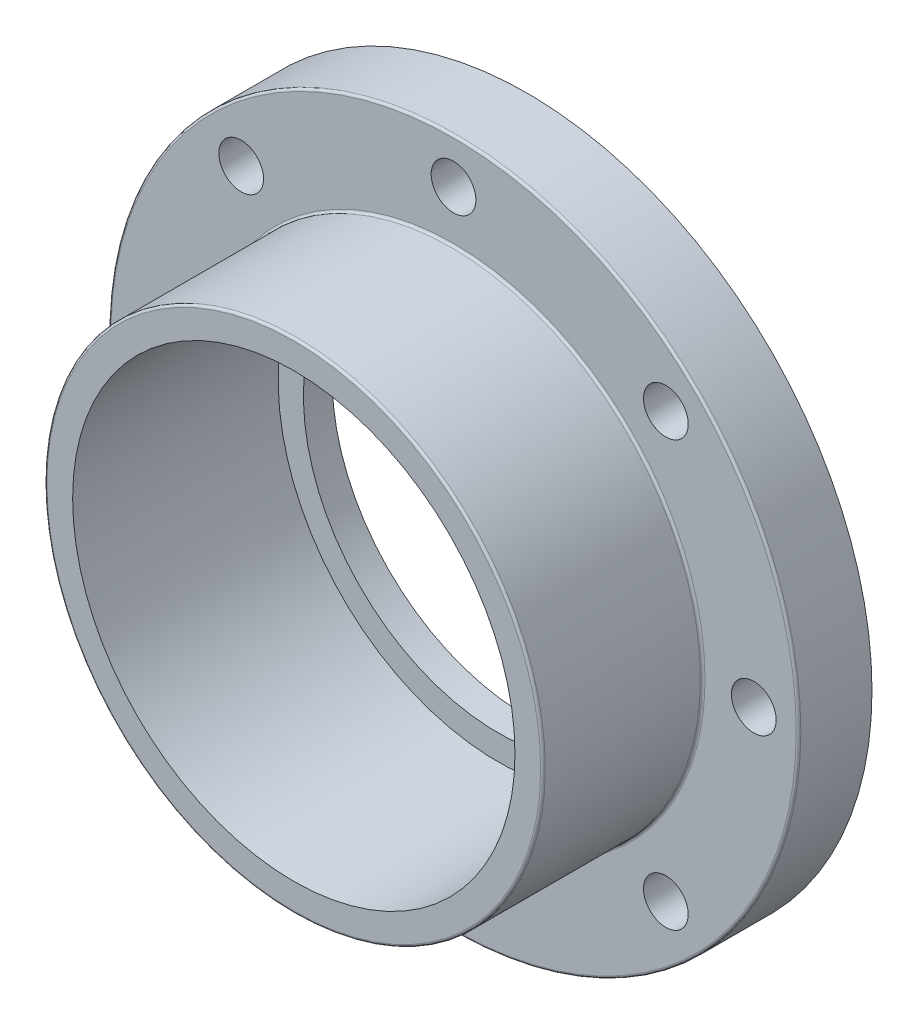
SolidWorks part; units mm, degrees
ref_plane "Front Plane" through (0, 0, 0) normal (0, 0, 1) x (1, 0, 0)
ref_plane "Top Plane" through (0, 0, 0) normal (0, 1, 0) x (1, 0, 0)
ref_plane "Right Plane" through (0, 0, 0) normal (1, 0, 0) x (0, 0, -1)
sketch "Sketch0" plane through (0, 0, 0) normal (1, 0, 0) x (0, 0, -1)
  line L0 (0, 0) -> (-115.8875, 0) construction
  point P3 (-36.5125, 0)
  point P4 (-14.2875, 0)
  dimension "Q" = 36.5125
  dimension "C" = 115.8875
  dimension "N" = 14.2875
sketch "Sketch1" plane through (0, 0, 0) normal (0, 0, 1) x (1, 0, 0)
  circle A0 centre (0, 0) radius 171.45
  circle A1 centre (0, 0) radius 109.9185 construction
  circle A2 centre (0, 0) radius 149.225 construction
  circle A3 centre (0, 149.225) radius 11.1125 construction
  circle A4 centre (0, 0) radius 123.825 construction
  circle A5 centre (0, 0) radius 96.8375 construction
  circle A6 centre (0, 0) radius 109.347 construction
  point P9 (0, 109.9185)
  point P10 (0, 109.347)
  point P11 (0, 96.8375)
  dimension "A" = 342.9
  dimension "B" = 298.45
  dimension "Bolt Hole Size" = 22.225
  dimension "Pipe OD A" = 219.837
  dimension "Hub OD" = 247.65
  dimension "Pipe ID" = 193.675
  dimension "Pipe OD B" = 218.694
extrude "Extrude1" add sketch "Sketch1" along normal up to vertex (36.5125 mm away) up to point (0, 0, 36.5125)
sketch "Sketch2" plane through (0, 0, 36.5125) normal (0, 0, 1) x (1, 0, 0)
  circle A0 centre (0, 0) radius 123.825 construction
  circle A1 centre (0, 0) radius 123.825
extrude "Extrude2" add sketch "Sketch2" along normal up to vertex (79.375 mm away) up to point (0, 0, 115.8875)
sketch "Sketch3" plane through (0, 0, 36.5125) normal (0, 0, 1) x (1, 0, 0)
  circle A0 centre (0, 149.225) radius 11.1125 construction
  circle A1 centre (0, 149.225) radius 11.1125
extrude "Extrude3" cut sketch "Sketch3" against normal through all
ref_axis "Axis1" through (0, 0, -5.7944) along (0, 0, 1)
pattern_circular "CirPattern1" count 8 over 360 about axis through (0, 0, -5.7944) along (0, 0, 1) of "Extrude3"
fillet "Fillet1" radius 1.1545 3 edges at (123.825, 0, 115.8875) (123.825, 0, 36.5125) (171.45, 0, 36.5125) tangent propagation no
sketch "Sketch4" plane through (0, 0, 63.5) normal (1, 0, 0) x (0, 0, -1)
  line L0 (-52.3875, 109.9185) -> (49.2125, 109.347)
  line L1 (49.2125, 109.347) -> (49.2125, 96.8375)
  line L2 (49.2125, 96.8375) -> (63.5, 96.8375)
  line L3 (63.5, 96.8375) -> (63.5, 0)
  line L4 (63.5, 0) -> (-52.3875, 0)
  line L5 (-52.3875, 0) -> (-52.3875, 109.9185)
  line L6 (63.5, 149.225) -> (63.5, -149.225) construction
  line L7 (49.2125, 0) -> (49.2125, 96.8375) construction
  line L8 (-52.3875, 109.9185) -> (63.5, 109.9185) construction
  line L12 (63.5, 109.347) -> (49.2125, 109.347) construction
revolve "Cut-Revolve1" cut sketch "Sketch4" angle 360 about L4
